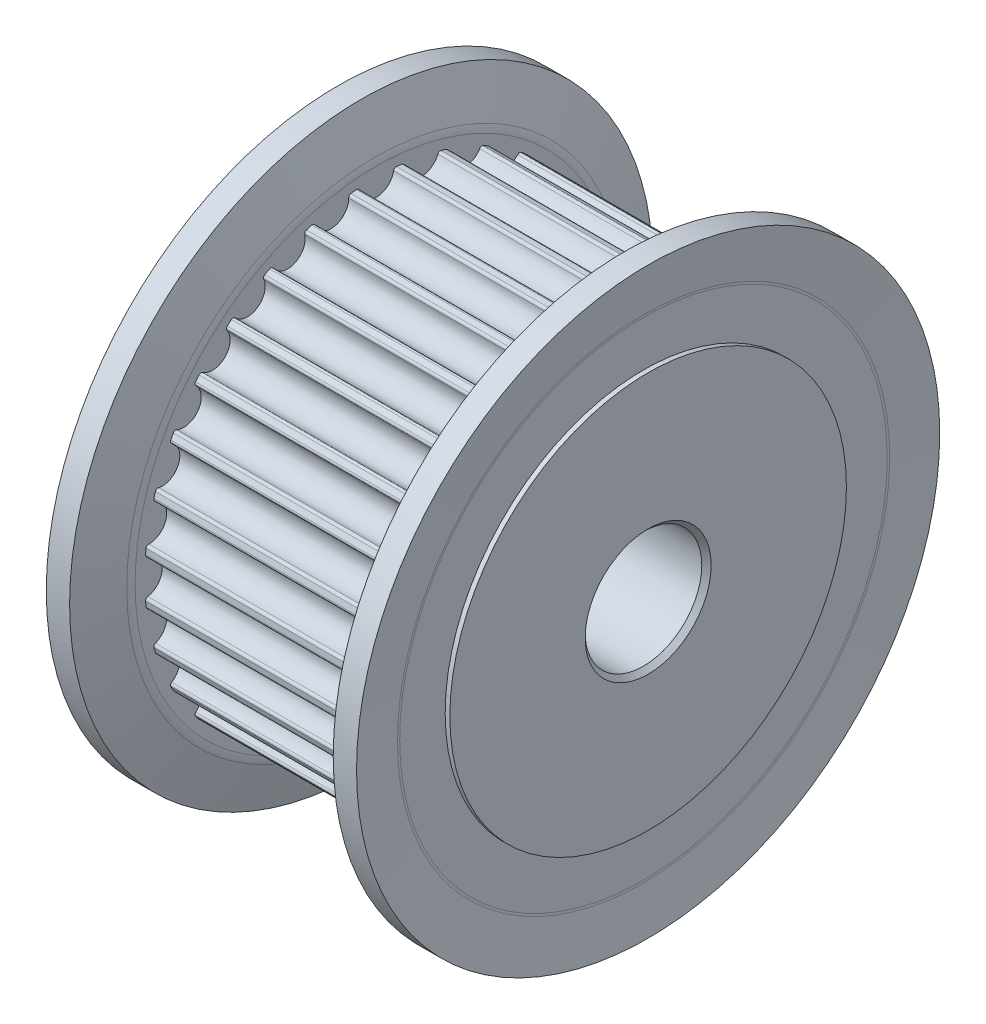
SolidWorks part; units mm, degrees
material "Aluminium"
ref_plane "Front Plane" through (0, 0, 0) normal (0, 0, 1) x (1, 0, 0)
ref_plane "Top Plane" through (0, 0, 0) normal (0, 1, 0) x (1, 0, 0)
ref_plane "Right Plane" through (0, 0, 0) normal (1, 0, 0) x (0, 0, -1)
other "Configuration Table"
sketch "Sketch1" plane through (0, 0, 0) normal (0, 0, 1) x (1, 0, 0)
  line L0 (11.3706, 0) -> (-11.3706, 0) construction
  line L1 (5, 8.5) -> (6.65, 8.5)
  line L2 (-6.65, 0) -> (6.65, 0)
  line L3 (-6.65, 0) -> (-6.65, 8.5)
  line L4 (-6.65, 8.5) -> (-5, 8.5)
  line L5 (6.65, 0) -> (6.65, 8.5)
  line L7 (-5, 8.5) -> (-5, 9.93)
  line L8 (-5, 9.93) -> (5, 9.93)
  line L9 (5, 8.5) -> (5, 9.93)
  line L10 (-5, 8.5) -> (5, 8.5) construction
  line L11 (0, 8.5) -> (0, 0) construction
  dimension "D2" = 1.65
  dimension "E" = 17
  dimension "OD" = 19.86
  dimension "A" = 10
revolve "Revolve1" add sketch "Sketch1" angle 360 about L0
sketch "Sketch2" plane through (0, 0, 0) normal (0, 0, 1) x (1, 0, 0)
  line L0 (5, 8.5) -> (5, 10.5)
  line L1 (5, 10.5) -> (5.65, 12.5)
  line L2 (5.65, 12.5) -> (6.65, 12.5)
  line L4 (6.45, 8.5) -> (5, 8.5)
  line L5 (0, 0) -> (0, 9.93) construction
  line L6 (5, 9.93) -> (-5, 9.93) construction
  line L7 (-6.45, 8.5) -> (-5, 8.5)
  line L9 (-5.65, 12.5) -> (-6.65, 12.5)
  line L10 (-5, 10.5) -> (-5.65, 12.5)
  line L11 (-5, 8.5) -> (-5, 10.5)
  line L12 (0, 0) -> (6.65, 0) construction
  line L13 (6.65, -8.5) -> (6.65, 8.5) construction
  line L14 (6.45, 8.5) -> (6.45, 10.5)
  line L15 (6.45, 10.5) -> (6.65, 12.5)
  line L16 (-6.45, 8.5) -> (-6.45, 10.5)
  line L17 (-6.45, 10.5) -> (-6.65, 12.5)
  line L18 (6.65, 12.5) -> (6.65, 8.5) construction
  line L19 (5, 10.5) -> (6.45, 10.5) construction
  line L20 (-6.65, 12.5) -> (-6.65, 8.5) construction
  line L21 (-5, 8.5) -> (-6.65, 8.5) construction
  line L22 (-5, 10.5) -> (-6.45, 10.5) construction
  dimension "D1" = 2
  dimension "D2" = 1
  dimension "D3" = 0.2
  dimension "F" = 25
revolve "Revolve2" add sketch "Sketch2" angle 360 about L12
fillet "Fillet1" radius 1 2 edges at (5, 0, 10.5) (6.45, 0, 10.5)
fillet "Fillet2" radius 1 2 edges at (-6.45, 0, 10.5) (-5, 0, 10.5)
sketch "Furo01" plane through (0, 0, 0) normal (1, 0, 0) x (0, 0, -1)
  circle A0 centre (0, 0) radius 2.5
  dimension "Hd1" = 5
extrude "Furo1" cut sketch "Furo01" against normal through all both and the other way through all
sketch "Sketch3" plane through (-6.65, 0, 0) normal (1, 0, 0) x (0, 0, -1)
  circle A0 centre (0, 0) radius 6.5
  circle A1 centre (0, 0) radius 2.5 construction
  circle A2 centre (0, 0) radius 2.5
  dimension "D" = 13
extrude "Boss-Extrude1" [suppressed] add sketch "Sketch3" along normal blind 21
chamfer "ChamferA" distance 0.2 angle 45 2 edges at (-6.65, 0, -2.5) (6.65, 0, -2.5)
chamfer "ChamferB" [suppressed] distance 0.2 angle 45
sketch "Sketch4" plane through (0, 0, 0) normal (1, 0, 0) x (0, 0, -1)
  line L0 (0, 9.931) -> (0, 0) construction
  line L1 (-0.7479, 9.8744) -> (-0.944, 12.4643)
  line L2 (-0.944, 12.4643) -> (0.944, 12.4643)
  line L3 (0.944, 12.4643) -> (0.7479, 9.8744)
  line L4 (0.7479, 9.8744) -> (0, 0) construction
  line L5 (-0.7479, 9.8744) -> (0, 0) construction
  circle A0 centre (0, 0) radius 10.185 construction
  arc A1 (-0.7479, 9.8744) -> (0.7479, 9.8744) centre (0, 9.931) ccw
  circle A2 centre (0, 0) radius 9.181 construction
  circle A4 centre (0, 0) radius 12.5 construction
  circle A5 centre (0, 0) radius 9.931 construction
  dimension "D1" = 0.254
  dimension "PD" = 20.37
  dimension "D2" = 0.75
extrude "Cut-Extrude1" cut sketch "Sketch4" against normal mid plane 10
fillet "Fillet3" radius 0.11 2 edges at (0, 9.9016, -0.7499) (0, 9.9016, 0.7499)
pattern_circular "CirPattern1" count 32 over 360 about axis through (0, 0, 0) along (1, 0, 0) of "Cut-Extrude1", "Fillet3"
sketch "Sketch5" [suppressed] plane through (0, 0, 0) normal (0, 1, 0) x (1, 0, 0)
  line L0 (12.85, 0) -> (10.5, 0) construction
  line L1 (12.85, -2.8) -> (12.85, 2.8) construction
  line L2 (10.5, 0) -> (10.5, 8.5) construction
  line L3 (14.15, 8.5) -> (6.85, 8.5) construction
  point P0 (10.5, 0)
hole_wizard "M3 Tapped Hole1" [suppressed] positions "Sketch5" profile "Sketch7" tap size "M3" standard "DIN"
sketch "Sketch7" plane through (10.5, 0, 0) normal (1, 0, 0) x (0, 0, -1)
  line L0 (0, 0) -> (0, 6.5)
  line L1 (0, 6.5) -> (1.25, 6.5)
  line L2 (1.25, 6.5) -> (1.25, 0)
  line L5 (1.25, 0) -> (0, 0)
  line L11 (0, -6.35) -> (0, 107.95) construction
  dimension "Thru Tap Drill Dia." = 2.5
  dimension "Thru Tap Drill Depth" = 6.5
cosmetic thread "Hole Thread1" parameters "D2"=3
pattern_circular "CirPattern2" [suppressed] count 2 every 120
